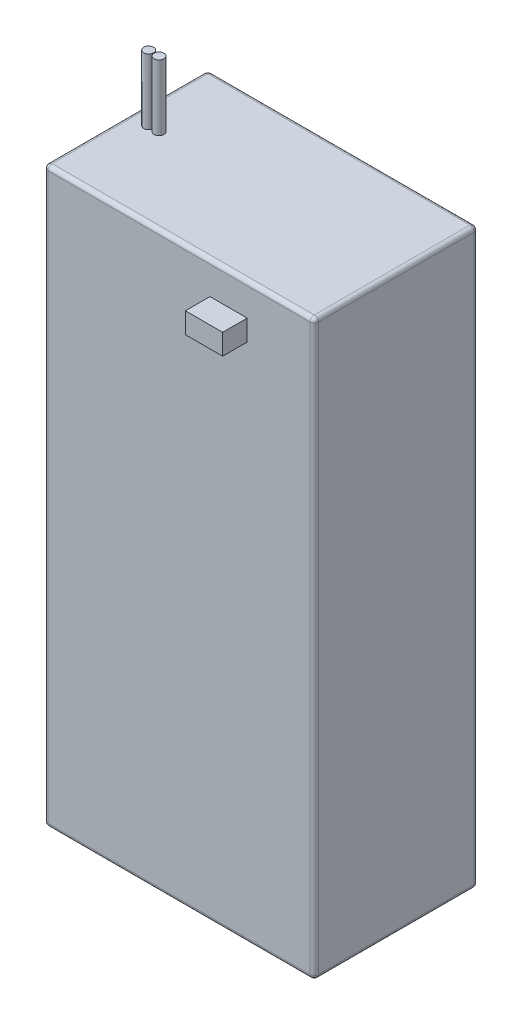
SolidWorks part; units mm, degrees
ref_plane "Front" through (0, 0, 0) normal (0, 0, 1) x (1, 0, 0)
ref_plane "Top" through (0, 0, 0) normal (0, 1, 0) x (1, 0, 0)
ref_plane "Right" through (0, 0, 0) normal (1, 0, 0) x (0, 0, -1)
sketch "Sketch1" plane through (0, 0, 0) normal (0, 0, 1) x (1, 0, 0)
  line L1 (-16.5, -35) -> (16.5, -35)
  line L2 (-16.5, -35) -> (-16.5, 35)
  line L3 (-16.5, 35) -> (16.5, 35)
  line L4 (16.5, -35) -> (16.5, 35)
  line L5 (-16.5, -35) -> (16.5, 35) construction
  line L6 (-16.5, 35) -> (16.5, -35) construction
  point P0 (0, 0)
  dimension "D1" = 70
  dimension "D2" = 33
extrude "Boss-Extrude1" add sketch "Sketch1" along normal blind 20
fillet "Fillet1" radius 0.5 12 edges at (-16.5, -35, 10) (16.5, -35, 10) (16.5, 35, 10) (-16.5, 35, 10) (0, 35, 0) (-16.5, 0, 0) (0, -35, 0) (16.5, 0, 0) (0, -35, 20) (-16.5, 0, 20) (0, 35, 20) (16.5, 0, 20)
sketch "Sketch2" plane through (0, 35, 0) normal (0, 1, 0) x (1, 0, 0)
  circle A0 centre (-14.1249, -9.5918) radius 0.6
  circle A1 centre (-12.8648, -9.5918) radius 0.6
  point P4 (0, 0)
  point P5 (-12.8648, -9.5918)
  dimension "D1" = 1.2
extrude "Wires" add sketch "Sketch2" along normal blind 8
sketch "Sketch3" plane through (0, 0, 20) normal (0, 0, 1) x (1, 0, 0)
  line L1 (3.7669, 31.0762) -> (8.3175, 31.0762)
  line L2 (3.7669, 31.0762) -> (3.7669, 28.5481)
  line L3 (3.7669, 28.5481) -> (8.3175, 28.5481)
  line L4 (8.3175, 31.0762) -> (8.3175, 28.5481)
  line L5 (3.7669, 31.0762) -> (8.3175, 28.5481) construction
  line L6 (3.7669, 28.5481) -> (8.3175, 31.0762) construction
  point P0 (6.0422, 29.8121)
  point P5 (6.8512, 28.447)
  point P6 (3.9186, 27.284)
  point P7 (6.0422, 29.8121)
extrude "Power Switch" add sketch "Sketch3" along normal blind 3
